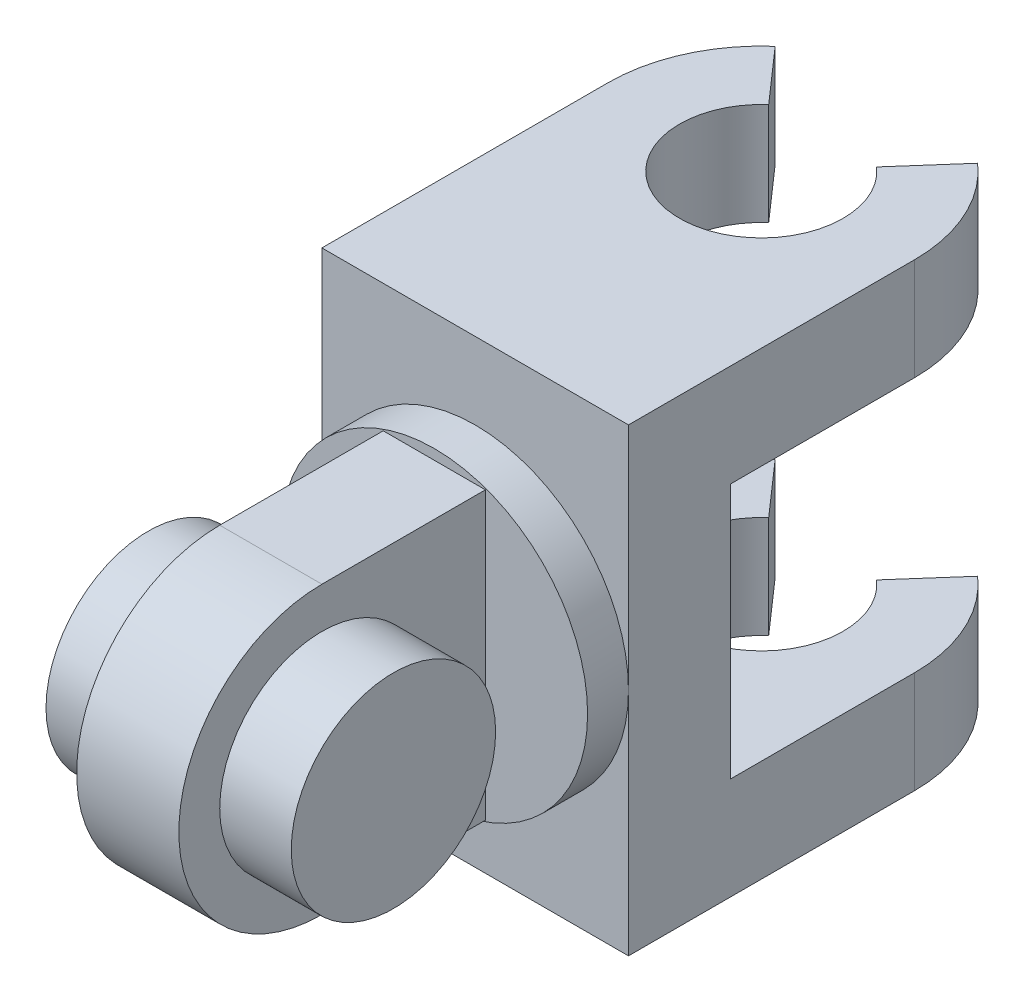
SolidWorks part; units mm, degrees
ref_plane "Front Plane" through (0, 0, 0) normal (0, 0, 1) x (1, 0, 0)
ref_plane "Top Plane" through (0, 0, 0) normal (0, 1, 0) x (1, 0, 0)
ref_plane "Right Plane" through (0, 0, 0) normal (1, 0, 0) x (0, 0, -1)
sketch "Sketch3" plane through (0, 0, 0) normal (1, 0, 0) x (0, 0, -1)
  circle A0 centre (0, 0) radius 10
  dimension "D1" = 20
extrude "Boss-Extrude2" add sketch "Sketch3" along normal mid plane 24
sketch "Sketch4" plane through (0, 0, 0) normal (1, 0, 0) x (0, 0, -1)
  line L0 (0, 14) -> (16, 14)
  line L1 (16, 14) -> (16, -14)
  line L2 (16, -14) -> (0, -14)
  arc A0 (0, -14) -> (0, 14) centre (0, 0) cw
  dimension "D1" = 14
  dimension "D2" = 16
extrude "Boss-Extrude3" add sketch "Sketch4" along normal mid plane 10
sketch "Sketch5" plane through (0, 0, -16) normal (0, 0, -1) x (-1, 0, 0)
  circle A0 centre (0, 0) radius 15
  dimension "D1" = 30
extrude "Boss-Extrude4" add sketch "Sketch5" along normal blind 4
sketch "Sketch6" plane through (0, 0, -20) normal (0, 0, -1) x (-1, 0, 0)
  line L1 (-15, 22.5) -> (15, 22.5)
  line L2 (-15, 22.5) -> (-15, -22.5)
  line L3 (-15, -22.5) -> (15, -22.5)
  line L4 (15, 22.5) -> (15, -22.5)
  line L5 (-15, 22.5) -> (15, -22.5) construction
  line L6 (-15, -22.5) -> (15, 22.5) construction
  point P0 (0, 0)
  dimension "D1" = 45
  dimension "D2" = 30
extrude "Boss-Extrude6" add sketch "Sketch6" along normal blind 10
sketch "Sketch7" plane through (0, 0, 0) normal (0, 1, 0) x (1, 0, 0)
  line L0 (-15, 30) -> (-15, 48)
  line L1 (15, 48) -> (15, 30)
  line L2 (15, 30) -> (-15, 30)
  arc A0 (-15, 48) -> (15, 48) centre (0, 48) cw
  circle A1 centre (0, 48) radius 8
  dimension "D2" = 16
  dimension "D1" = 18
extrude "Boss-Extrude7" add sketch "Sketch7" along normal up to vertex (22.5 mm away) from offset 12.5 up to point (15, 22.5, -30)
extrude "Boss-Extrude8" add sketch "Sketch7<2>" against normal up to vertex (22.5 mm away) from offset 12.5 up to point (15, -22.5, -30) offset against normal yes
sketch "Sketch7<2>" plane through (0, 0, 0) normal (0, 1, 0) x (1, 0, 0) same geometry as "Sketch7"
sketch "Sketch8" plane through (0, 22.5, 0) normal (0, 1, 0) x (1, 0, 0)
  line L0 (-9.9092, 59.2609) -> (-5.2849, 54.0058)
  line L1 (9.9092, 59.2609) -> (5.2849, 54.0058)
  line L3 (-15, 20) -> (15, 20)
  line L4 (15, 20) -> (15, 48)
  line L5 (-15, 48) -> (-15, 20)
  circle A0 centre (0, 48) radius 8 construction
  arc A1 (15, 48) -> (-15, 48) centre (0, 48) ccw
  arc A2 (9.9092, 59.2609) -> (-9.9092, 59.2609) centre (0, 48) ccw
  arc A3 (5.2849, 54.0058) -> (-5.2849, 54.0058) centre (0, 48) ccw
  dimension "D1" = 0
extrude "Cut-Extrude1" cut sketch "Sketch8" against normal up to surface (45 mm away) up to face at (0, -22.5, -37.75)
